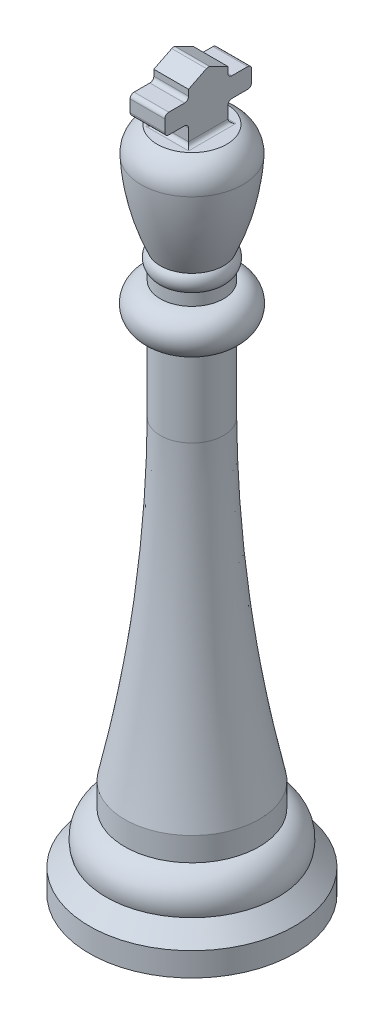
SolidWorks part; units mm, degrees
ref_plane "Front Plane" through (0, 0, 0) normal (0, 0, 1) x (1, 0, 0)
ref_plane "Top Plane" through (0, 0, 0) normal (0, 1, 0) x (1, 0, 0)
ref_plane "Right Plane" through (0, 0, 0) normal (1, 0, 0) x (0, 0, -1)
sketch "Sketch1" plane through (0, 0, 0) normal (0, 0, 1) x (1, 0, 0)
  line L0 (0, 0) -> (6.604, 0)
  line L1 (0, 0) -> (0, 42.926)
  line L2 (6.604, 0) -> (6.604, 1.524)
  line L3 (6.604, 1.524) -> (5.5264, 2.6016)
  line L4 (4.3243, 4.8102) -> (4.3243, 6.3342)
  line L5 (2.0374, 26.5948) -> (2.0374, 31.6748)
  line L6 (2.0374, 34.2148) -> (2.0374, 34.9768)
  line L8 (2.2343, 42.926) -> (0, 42.926)
  arc A0 (5.5264, 2.6016) -> (4.3243, 4.8102) centre (3.8211, 3.1049) ccw
  arc A1 (2.0374, 31.6748) -> (2.0374, 34.2148) centre (2.0374, 32.9448) ccw
  arc A2 (2.0374, 34.9768) -> (2.0374, 36.0544) centre (1.4985, 35.5156) ccw
  arc A3 (3.2797, 41.1965) -> (2.2343, 42.926) centre (1.505, 41.3044) ccw
  spline S0 degree 2 poles (4.3243, 6.3342) (2.1004, 16.3148) (2.0374, 26.5948) knots 0 0 0 1 1 1
  spline S1 degree 3 poles (2.0374, 36.0544) (2.7546, 37.6906) (3.1715, 39.4171) (3.2797, 41.1965) knots 0 0 0 0 0.825529 0.825529 0.825529 0.825529
  point P18 (0, 0)
  dimension "D6" = 1.778
  dimension "D9" = 1.27
  dimension "D11" = 0.762
  dimension "D12" = 1.778
  dimension "D1" = 6.604
  dimension "D2" = 42.926
  dimension "D3" = 90
  dimension "D4" = 1.524
  dimension "D5" = 1.524
  dimension "D7" = 1.524
  dimension "D8" = 5.08
  dimension "D10" = 0.762
  dimension "D14" = 2.2343
revolve "Revolve1" add sketch "Sketch1" angle 360 about L1
sketch "Sketch3" plane through (0, 42.926, 0) normal (0, 1, 0) x (1, 0, 0)
  line L2 (1.1171, 1.9349) -> (-1.1171, 1.9349)
  line L5 (-1.1171, -1.9349) -> (1.1171, -1.9349)
  line L7 (-1.1171, 1.9349) -> (1.1171, 1.9349)
  line L8 (-1.1171, 1.9349) -> (-1.1171, -1.9349)
  line L9 (-1.1171, -1.9349) -> (1.1171, -1.9349)
  line L10 (1.1171, 1.9349) -> (1.1171, -1.9349)
  line L11 (-1.1171, 1.9349) -> (-2.2343, 0) [skipped]
  line L12 (-2.2343, 0) -> (-1.1171, -1.9349) [skipped]
  line L13 (1.1171, -1.9349) -> (2.2343, 0) [skipped]
  line L14 (2.2343, 0) -> (1.1171, 1.9349) [skipped]
extrude "Boss-Extrude1" add sketch "Sketch3" along normal blind 3.81 contours L10 L2 L8 L5 region at (0, 42.926, 0)
sketch "Sketch4" plane through (0, 0, -1.9349) normal (0, 0, -1) x (-1, 0, 0)
  line L1 (-1.1171, 46.736) -> (1.1171, 46.736)
  line L2 (-1.1171, 46.736) -> (-1.1171, 42.926)
  line L3 (-1.1171, 42.926) -> (1.1171, 42.926)
  line L4 (1.1171, 46.736) -> (1.1171, 42.926)
extrude "Boss-Extrude2" add sketch "Sketch4" along normal blind 1.27
sketch "Sketch7" plane through (0, 0, 1.9349) normal (0, 0, 1) x (1, 0, 0)
  line L1 (-1.1171, 46.736) -> (1.1171, 46.736)
  line L2 (-1.1171, 46.736) -> (-1.1171, 42.926)
  line L3 (-1.1171, 42.926) -> (1.1171, 42.926)
  line L4 (1.1171, 46.736) -> (1.1171, 42.926)
extrude "Boss-Extrude3" add sketch "Sketch7" along normal blind 1.27
sketch "Sketch11" plane through (1.1171, 0, 0) normal (1, 0, 0) x (0, 0, -1)
  line L0 (-1.3381, 42.926) -> (1.2019, 42.926)
  line L1 (1.9349, 42.926) -> (-1.9349, 42.926) construction
  line L2 (-0.0681, 42.926) -> (-0.0681, 46.736) construction
  line L3 (3.2049, 46.736) -> (-3.2049, 46.736) construction
  line L4 (1.2019, 42.926) -> (1.2019, 43.942)
  line L5 (1.4559, 44.196) -> (2.4719, 44.196)
  line L6 (2.7259, 44.45) -> (2.7259, 45.212)
  line L7 (2.4719, 45.466) -> (1.4559, 45.466)
  line L8 (1.2019, 45.72) -> (1.2019, 46.1062)
  line L9 (1.2019, 46.1062) -> (0.0447, 46.68)
  line L10 (-1.3381, 42.926) -> (-1.3381, 43.942)
  line L11 (-1.5921, 44.196) -> (-2.6081, 44.196)
  line L12 (-2.8621, 44.45) -> (-2.8621, 45.212)
  line L13 (-2.6081, 45.466) -> (-1.5921, 45.466)
  line L14 (-1.3381, 45.72) -> (-1.3381, 46.1062)
  line L15 (-1.3381, 46.1062) -> (-0.181, 46.68)
  arc A0 (-1.3381, 43.942) -> (-1.5921, 44.196) centre (-1.5921, 43.942) ccw
  arc A1 (1.2019, 43.942) -> (1.4559, 44.196) centre (1.4559, 43.942) cw
  arc A2 (2.4719, 44.196) -> (2.7259, 44.45) centre (2.4719, 44.45) ccw
  arc A3 (2.7259, 45.212) -> (2.4719, 45.466) centre (2.4719, 45.212) ccw
  arc A4 (-2.8621, 45.212) -> (-2.6081, 45.466) centre (-2.6081, 45.212) cw
  arc A5 (-2.6081, 44.196) -> (-2.8621, 44.45) centre (-2.6081, 44.45) cw
  arc A6 (0.0447, 46.68) -> (-0.181, 46.68) centre (-0.0681, 46.4525) ccw
  arc A7 (1.4559, 45.466) -> (1.2019, 45.72) centre (1.4559, 45.72) cw
  arc A8 (-1.5921, 45.466) -> (-1.3381, 45.72) centre (-1.5921, 45.72) ccw
  point P5 (-0.0681, 42.926)
  point P21 (-1.3381, 44.196)
  point P24 (1.2019, 44.196)
  point P27 (2.7259, 44.196)
  point P30 (2.7259, 45.466)
  point P33 (-2.8621, 45.466)
  point P36 (-2.8621, 44.196)
  point P42 (1.2019, 45.466)
  point P45 (-1.3381, 45.466)
  point P46 (0, 0)
  line M15 (-3.2049, 42.926) -> (-1.9349, 42.926)
  line M16 (-1.9349, 42.926) -> (1.9349, 42.926)
  line M17 (1.9349, 42.926) -> (3.2049, 42.926)
  line M18 (3.2049, 42.926) -> (3.2049, 46.736)
  line M19 (3.2049, 46.736) -> (-3.2049, 46.736)
  line M20 (-3.2049, 46.736) -> (-3.2049, 42.926)
  dimension "D7" = 0.254
  dimension "D1" = 2.54
  dimension "D2" = 1.27
  dimension "D3" = 1.524
  dimension "D4" = 1.27
  dimension "D5" = 1.524
  dimension "D6" = 0.6402
extrude "Cut-Extrude3" cut sketch "Sketch11" against normal blind 2.286 contours A6 L2 L10 A0 L11 A5 L12 A4 L13 A8 L14 L15 M19 M20 M15 M16 | L2 A6 L9 L8 A7 L7 A3 L6 A2 L5 A1 L4 M16 M17 M18 M19 region at (1.1171, 42.9754, 1.6365) region at (1.1171, 43.434, -1.2521)
fillet "Fillet1" radius 0.254 4 edges at (0, 42.926, -1.2019) (1.1171, 42.926, 0.0681) (-1.1171, 42.926, 0.0681) (0, 42.926, 1.3381)
